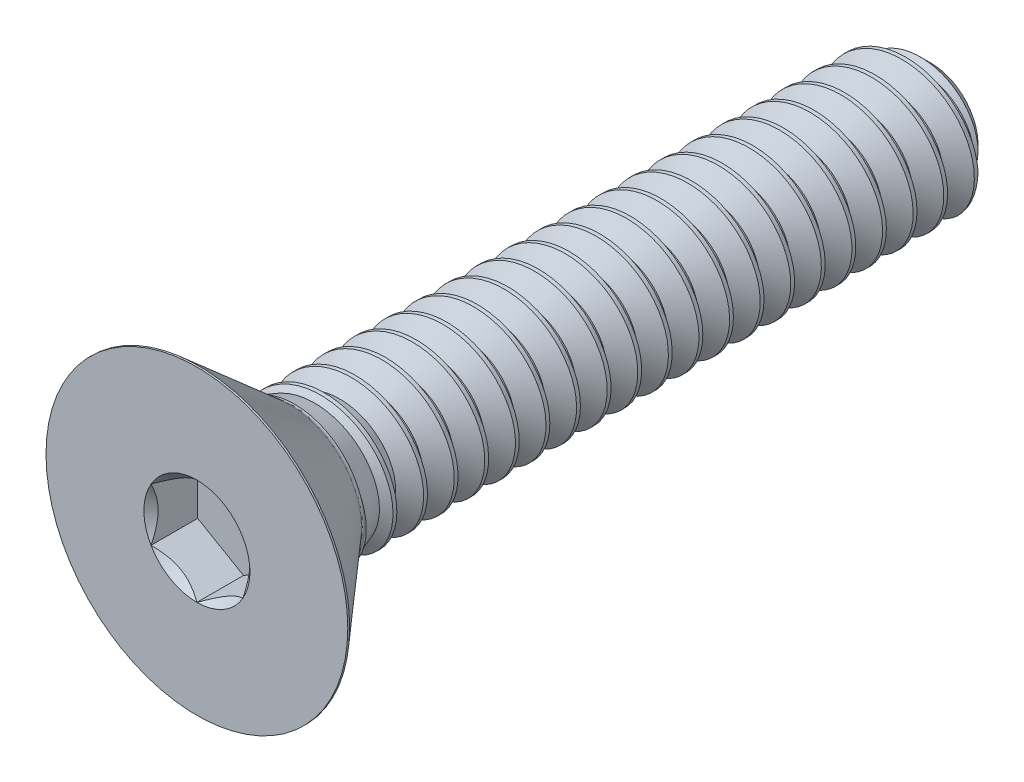
SolidWorks part; units mm, degrees
material "Alloy Steel"
ref_plane "Front Plane" through (0, 0, 0) normal (0, 0, 1) x (1, 0, 0)
ref_plane "Top Plane" through (0, 0, 0) normal (0, 1, 0) x (1, 0, 0)
ref_plane "Right Plane" through (0, 0, 0) normal (1, 0, 0) x (0, 0, -1)
sketch "Sketch1" plane through (0, 0, 0) normal (1, 0, 0) x (0, 0, -1)
  line L0 (-12.7, 0) -> (12.7, 0) construction
  line L1 (-12.7, 0) -> (-12.7, 5.2197)
  line L2 (-12.7, 5.2197) -> (-12.6355, 5.2197)
  line L3 (-12.6355, 5.2197) -> (-9.4742, 2.4716)
  line L4 (-12.6355, -5.2197) -> (-9.4742, -2.4716)
  line L5 (12.7, 0) -> (12.7, 2.413)
  line L6 (12.7, 2.413) -> (-9.4742, 2.413)
  line L7 (11.9062, 2.413) -> (12.7, 1.6192)
  line L8 (12.6339, 2.5276) -> (13.163, 1.611) construction
  line L9 (13.163, 1.611) -> (13.6922, 2.5276) construction
  line L10 (13.6922, 2.5276) -> (12.6339, 2.5276) construction
  line L11 (12.6669, 2.4703) -> (13.6591, 2.4703)
  line L12 (13.6591, 2.4703) -> (13.2292, 1.7256)
  line L13 (13.2292, 1.7256) -> (13.0969, 1.7256)
  line L14 (13.0969, 1.7256) -> (12.6669, 2.4703)
  line L15 (13.163, 1.7256) -> (13.163, 1.611) construction
  line L16 (12.7, 2.413) -> (13.626, 2.413) construction
  line L17 (13.163, 2.5276) -> (13.163, 2.413) construction
  line L18 (12.7, -2.413) -> (-9.4742, -2.413)
  arc A0 (-9.4742, 2.4716) -> (-9.3174, 2.413) centre (-9.3174, 2.6521) ccw
  point P2 (0, 0)
  point P23 (-11.0871, 0)
  point P27 (13.163, 2.4703)
  point P30 (11.1125, -2.413)
  point P31 (-6.7075, 2.413)
  point P32 (10.0901, 2.413)
  point P33 (-9.4742, 5.2197)
  point P34 (-12.6355, -5.2197)
  point P37 (-6.0551, 2.413)
  dimension "Length" = 25.4
  dimension "Head Height" = 3.2258
  dimension "Head Diameter" = 10.4394
  dimension "Countersink Angle" = 82
  dimension "Screw Size Decimal Equivalent" = 4.826
  dimension "Pitch" = 1.0583
  dimension "D4" = 0.1323
  dimension "D3" = 45
  dimension "D5" = 0.7938
  dimension "D6" = 1.6129
  dimension "D1" = 1.5875
  dimension "D7" = 2.6098
  dimension "D8" = 2.6098
  dimension "D9" = 3.2623
  dimension "D2" = 0.0645
sketch "Sketch8" plane through (0, 0, 0) normal (0, 0, 1) x (1, 0, 0)
  line L1 (0, 1.8331) -> (-1.5875, 0.9165)
  line L2 (-1.5875, 0.9165) -> (-1.5875, -0.9165)
  line L3 (-1.5875, -0.9165) -> (0, -1.8331)
  line L4 (0, -1.8331) -> (1.5875, -0.9165)
  line L5 (1.5875, -0.9165) -> (1.5875, 0.9165)
  line L6 (1.5875, 0.9165) -> (0, 1.8331)
  circle A0 centre (0, 0) radius 1.5875 construction
  dimension "Drive Size" = 3.175
sketch "Sketch2" plane through (0, 0, 0) normal (1, 0, 0) x (0, 0, -1)
  line L0 (-12.6355, 5.2197) -> (-9.4742, 2.4716) construction
  line L1 (-12.7, 0) -> (-12.7, 5.2197) construction
  line L2 (-12.6355, 5.2197) -> (-9.4742, 2.4716)
  line L3 (-12.7, 0) -> (-12.7, 5.2197)
  line L4 (-12.7, 5.2197) -> (-12.6355, 5.2197) construction
  line L5 (-12.7, 5.2197) -> (-12.6355, 5.2197)
  line L6 (-9.3174, 2.413) -> (11.9062, 2.413)
  line L7 (11.9062, 2.413) -> (12.7, 1.6192)
  line L8 (12.7, 1.6192) -> (12.7, 0)
  line L9 (12.7, 0) -> (-12.7, 0)
  arc A0 (-9.4742, 2.4716) -> (-9.3174, 2.413) centre (-9.3174, 2.6521) ccw construction
  arc A1 (-9.4742, 2.4716) -> (-9.3174, 2.413) centre (-9.3174, 2.6521) ccw
revolve "Revolve1" add sketch "Sketch2" angle 360 about L9
sketch "Sketch9" plane through (0, 0, 12.7) normal (0, 0, 1) x (1, 0, 0)
  line L0 (1.5875, -0.9165) -> (1.5875, 0.9165) construction
  line L1 (0, -1.8331) -> (1.5875, -0.9165) construction
  line L2 (-1.5875, -0.9165) -> (0, -1.8331) construction
  line L3 (-1.5875, 0.9165) -> (-1.5875, -0.9165) construction
  line L4 (0, 1.8331) -> (-1.5875, 0.9165) construction
  line L5 (1.5875, 0.9165) -> (0, 1.8331) construction
  line L6 (1.5875, -0.9165) -> (1.5875, 0.9165)
  line L7 (0, -1.8331) -> (1.5875, -0.9165)
  line L8 (-1.5875, -0.9165) -> (0, -1.8331)
  line L9 (-1.5875, 0.9165) -> (-1.5875, -0.9165)
  line L10 (0, 1.8331) -> (-1.5875, 0.9165)
  line L11 (1.5875, 0.9165) -> (0, 1.8331)
sketch "Sketch10" plane through (0, 0, 12.7) normal (0, 0, 1) x (1, 0, 0)
  circle A0 centre (0, 0) radius 1.8331
extrude "Cut-Extrude2" cut sketch "Sketch10" against normal up to vertex (1.6129 mm away) draft 45 up to point (0, 0, 11.0871)
extrude "Cut-Extrude1" cut sketch "Sketch9" against normal up to vertex (1.6129 mm away) up to point (0, 0, 11.0871)
ref_plane "Plane1" through (0, 0, 9.3174) normal (0, 0, 1) x (1, 0, 0)
split "Split1" trim tools "Plane1" bodies to split 111 resulting bodies 105 106
sketch "Sketch3" plane through (0, 0, -12.7) normal (0, 0, -1) x (-1, 0, 0)
  circle A0 centre (0, 0) radius 2.413 construction
  circle A1 centre (0, 0) radius 2.413
curve "Helix/Spiral1" pitch 1.0583 height 25.4 radius 2.413 centre (0, 0, -12.7) axis (0, 0, 1) start towards (0, 1, 0)
sketch "Sketch4" plane through (0, 0, 0) normal (1, 0, 0) x (0, 0, -1)
  line L0 (12.6669, 2.4703) -> (13.6591, 2.4703) construction
  line L1 (13.0969, 1.7256) -> (12.6669, 2.4703) construction
  line L2 (13.2292, 1.7256) -> (13.0969, 1.7256) construction
  line L3 (13.6591, 2.4703) -> (13.2292, 1.7256) construction
  line L4 (12.6669, 2.4703) -> (13.6591, 2.4703)
  line L5 (13.0969, 1.7256) -> (12.6669, 2.4703)
  line L6 (13.2292, 1.7256) -> (13.0969, 1.7256)
  line L7 (13.6591, 2.4703) -> (13.2292, 1.7256)
sweep "Cut-Sweep1" cut profiles "Sketch4" path "Helix/Spiral1" align with end faces yes
sketch "Sketch7" plane through (0, 0, 9.3174) normal (0, 0, 1) x (1, 0, 0)
  circle A0 centre (0, 0) radius 2.413
extrude "Boss-Extrude2" add sketch "Sketch7" against normal up to next (22.0174 mm away) draft 20
equation "\"D4@Sketch1\" = \"Pitch@Sketch1\" / 8"
equation "\"D5@Sketch1\"=\"Pitch@Sketch1\"*0.75"
equation "\"D4@Helix/Spiral1\"=\"Pitch@Sketch1\""
equation "\"D3@Helix/Spiral1\"=\"Length@Sketch1\""
equation "\"D6@Sketch1\"=\"Head Height@Sketch1\"/2"
equation "\"D1@Sketch1\"=\"Pitch@Sketch1\"*1.5"
equation "\"D7@Sketch1\"=\"Head Diameter@Sketch1\"*0.25"
equation "\"D8@Sketch1\"=\"D7@Sketch1\""
equation "\"D9@Sketch1\"=1.25*\"D7@Sketch1\""
